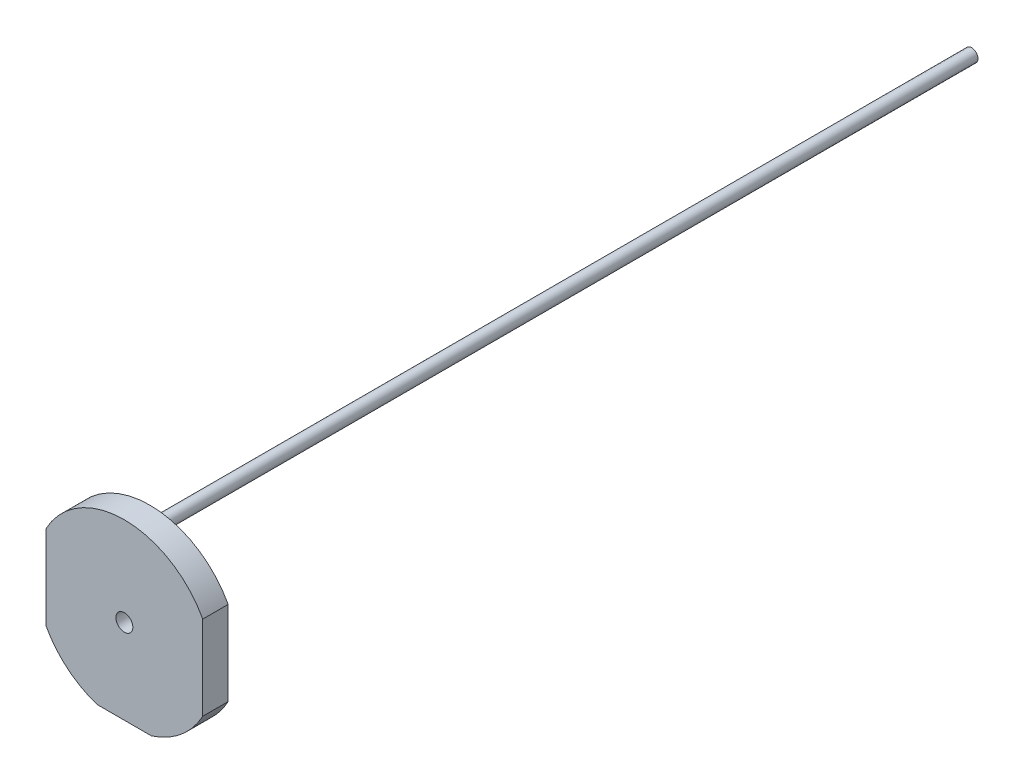
SolidWorks part; units mm, degrees
ref_plane "前视基准面" through (0, 0, 0) normal (0, 0, 1) x (1, 0, 0)
ref_plane "上视基准面" through (0, 0, 0) normal (0, 1, 0) x (1, 0, 0)
ref_plane "右视基准面" through (0, 0, 0) normal (1, 0, 0) x (0, 0, -1)
other "Configuration Table"
sketch "草图1" plane through (0, 0, 0) normal (0, 0, 1) x (1, 0, 0)
  line L0 (-6.4031, -20) -> (6.4031, -20)
  line L6 (-18.5, -9.9373) -> (-18.5, 9.9373)
  line L8 (18.5, -9.9373) -> (18.5, 9.9373)
  line L9 (-18.5, -9.9373) -> (18.5, 9.9373) construction
  line L10 (-18.5, 9.9373) -> (18.5, -9.9373) construction
  arc A4 (-18.5, -9.9373) -> (-6.4031, -20) centre (0, 0) ccw
  arc A5 (18.5, 9.9373) -> (-18.5, 9.9373) centre (0, 0) ccw
  arc A6 (6.4031, -20) -> (18.5, -9.9373) centre (0, 0) ccw
  circle A7 centre (0, 0) radius 2
  circle A8 centre (0, 16) radius 1.5
  dimension "D3" = 37
  dimension "D4" = 3
  dimension "D1" = 21
  dimension "D5" = 4
  dimension "D2" = 20
  dimension "D6" = 16
extrude "凸台-拉伸1" add sketch "草图1" against normal blind 6
extrude "凸台-拉伸2" add sketch "草图1<2>" against normal blind 200 contours A8 region at (0, 16, 0)
sketch "草图1<2>" plane through (0, 0, 0) normal (0, 0, 1) x (1, 0, 0) same geometry as "草图1"
